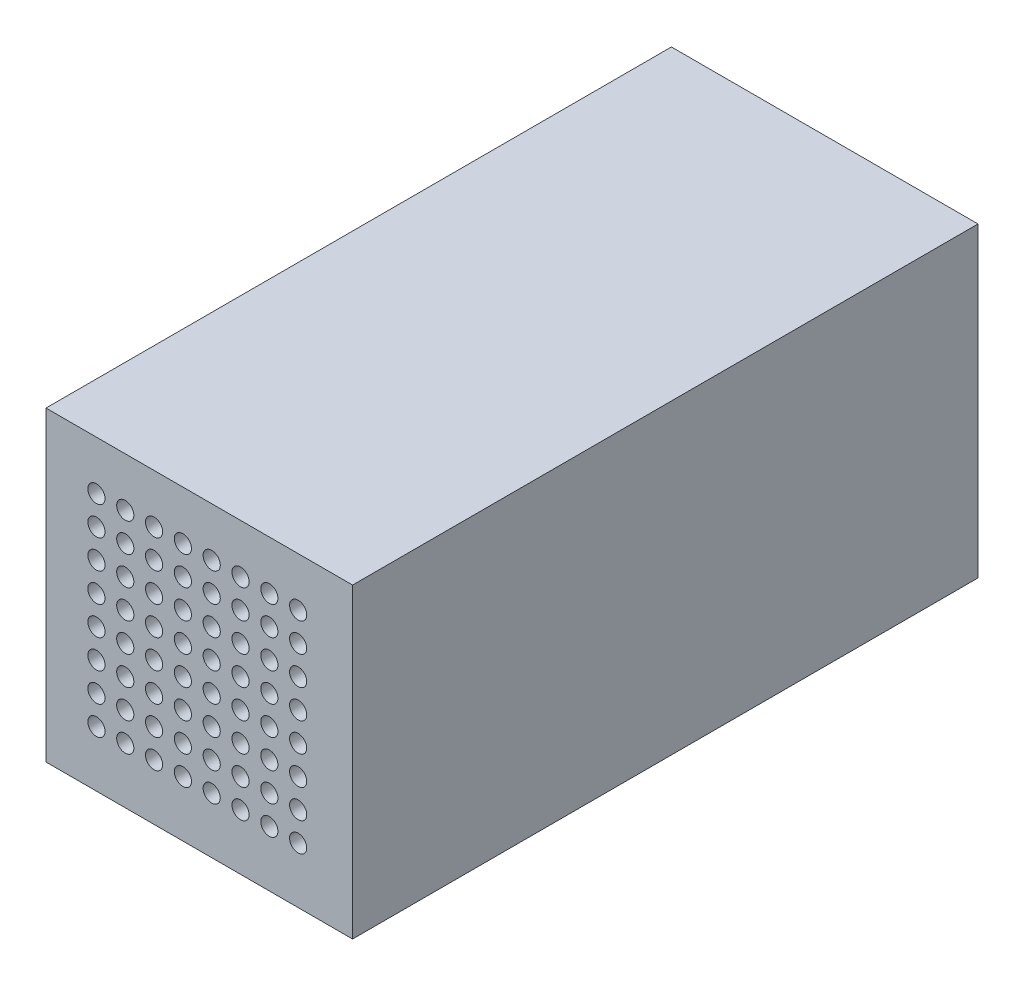
SolidWorks part; units mm, degrees
ref_plane "Front Plane" through (0, 0, 0) normal (0, 0, 1) x (1, 0, 0)
ref_plane "Top Plane" through (0, 0, 0) normal (0, 1, 0) x (1, 0, 0)
ref_plane "Right Plane" through (0, 0, 0) normal (1, 0, 0) x (0, 0, -1)
ref_plane "Plane1" through (0, 0, 43) normal (0, 0, 1) x (1, 0, 0)
sketch "Sketch2" plane through (0, 0, 43) normal (0, 0, 1) x (1, 0, 0)
  line L1 (-10, 10) -> (10, 10)
  line L2 (-10, 10) -> (-10, -10)
  line L3 (-10, -10) -> (10, -10)
  line L4 (10, 10) -> (10, -10)
  line L5 (-12.5, 12.5) -> (12.5, 12.5)
  line L6 (-12.5, 12.5) -> (-12.5, -12.5)
  line L7 (-12.5, -12.5) -> (12.5, -12.5)
  line L8 (12.5, 12.5) -> (12.5, -12.5)
  dimension "D1" = 20
  dimension "D2" = 20
  dimension "D3" = 25
  dimension "D4" = 25
  dimension "D5" = 10
  dimension "D6" = 10
  dimension "D7" = 12.5
  dimension "D8" = 12.5
sketch "Sketch5" plane through (0, 0, 43) normal (0, 0, 1) x (1, 0, 0)
  circle A0 centre (-8.3881, 8.5096) radius 0.7
  circle A1 centre (-6.0381, 8.5096) radius 0.7
  circle A2 centre (-3.6881, 8.5096) radius 0.7
  circle A3 centre (-1.3381, 8.5096) radius 0.7
  circle A4 centre (1.0119, 8.5096) radius 0.7
  circle A5 centre (3.3619, 8.5096) radius 0.7
  circle A6 centre (5.7119, 8.5096) radius 0.7
  circle A7 centre (8.0619, 8.5096) radius 0.7
  circle A8 centre (-6.0381, 6.1596) radius 0.7
  circle A9 centre (-3.6881, 6.1596) radius 0.7
  circle A10 centre (-1.3381, 6.1596) radius 0.7
  circle A11 centre (1.0119, 6.1596) radius 0.7
  circle A12 centre (3.3619, 6.1596) radius 0.7
  circle A13 centre (5.7119, 6.1596) radius 0.7
  circle A14 centre (8.0619, 6.1596) radius 0.7
  circle A15 centre (-6.0381, 3.8096) radius 0.7
  circle A16 centre (-3.6881, 3.8096) radius 0.7
  circle A17 centre (-1.3381, 3.8096) radius 0.7
  circle A18 centre (1.0119, 3.8096) radius 0.7
  circle A19 centre (3.3619, 3.8096) radius 0.7
  circle A20 centre (5.7119, 3.8096) radius 0.7
  circle A21 centre (8.0619, 3.8096) radius 0.7
  circle A22 centre (-6.0381, 1.4596) radius 0.7
  circle A23 centre (-3.6881, 1.4596) radius 0.7
  circle A24 centre (-1.3381, 1.4596) radius 0.7
  circle A25 centre (1.0119, 1.4596) radius 0.7
  circle A26 centre (3.3619, 1.4596) radius 0.7
  circle A27 centre (5.7119, 1.4596) radius 0.7
  circle A28 centre (8.0619, 1.4596) radius 0.7
  circle A29 centre (-6.0381, -0.8904) radius 0.7
  circle A30 centre (-3.6881, -0.8904) radius 0.7
  circle A31 centre (-1.3381, -0.8904) radius 0.7
  circle A32 centre (1.0119, -0.8904) radius 0.7
  circle A33 centre (3.3619, -0.8904) radius 0.7
  circle A34 centre (5.7119, -0.8904) radius 0.7
  circle A35 centre (8.0619, -0.8904) radius 0.7
  circle A36 centre (-6.0381, -3.2404) radius 0.7
  circle A37 centre (-3.6881, -3.2404) radius 0.7
  circle A38 centre (-1.3381, -3.2404) radius 0.7
  circle A39 centre (1.0119, -3.2404) radius 0.7
  circle A40 centre (3.3619, -3.2404) radius 0.7
  circle A41 centre (5.7119, -3.2404) radius 0.7
  circle A42 centre (8.0619, -3.2404) radius 0.7
  circle A43 centre (-6.0381, -5.5904) radius 0.7
  circle A44 centre (-3.6881, -5.5904) radius 0.7
  circle A45 centre (-1.3381, -5.5904) radius 0.7
  circle A46 centre (1.0119, -5.5904) radius 0.7
  circle A47 centre (3.3619, -5.5904) radius 0.7
  circle A48 centre (5.7119, -5.5904) radius 0.7
  circle A49 centre (8.0619, -5.5904) radius 0.7
  circle A50 centre (-6.0381, -7.9404) radius 0.7
  circle A51 centre (-3.6881, -7.9404) radius 0.7
  circle A52 centre (-1.3381, -7.9404) radius 0.7
  circle A53 centre (1.0119, -7.9404) radius 0.7
  circle A54 centre (3.3619, -7.9404) radius 0.7
  circle A55 centre (5.7119, -7.9404) radius 0.7
  circle A56 centre (8.0619, -7.9404) radius 0.7
  circle A57 centre (-8.3881, 6.1596) radius 0.7
  circle A58 centre (-8.3881, 3.8096) radius 0.7
  circle A59 centre (-8.3881, 1.4596) radius 0.7
  circle A60 centre (-8.3881, -0.8904) radius 0.7
  circle A61 centre (-8.3881, -3.2404) radius 0.7
  circle A62 centre (-8.3881, -5.5904) radius 0.7
  circle A63 centre (-8.3881, -7.9404) radius 0.7
  dimension "D1" = 8
  dimension "D2" = 8
extrude "Boss-Extrude1" add sketch "Sketch2" along normal blind 8 contours L6 L7 L8 L5
extrude "Cut-Extrude2" cut sketch "Sketch5" along normal blind 8
extrude "Boss-Extrude2" add sketch "Sketch2<6>" against normal blind 43
sketch "Sketch2<6>" plane through (0, 0, 43) normal (0, 0, 1) x (1, 0, 0) same geometry as "Sketch2"
